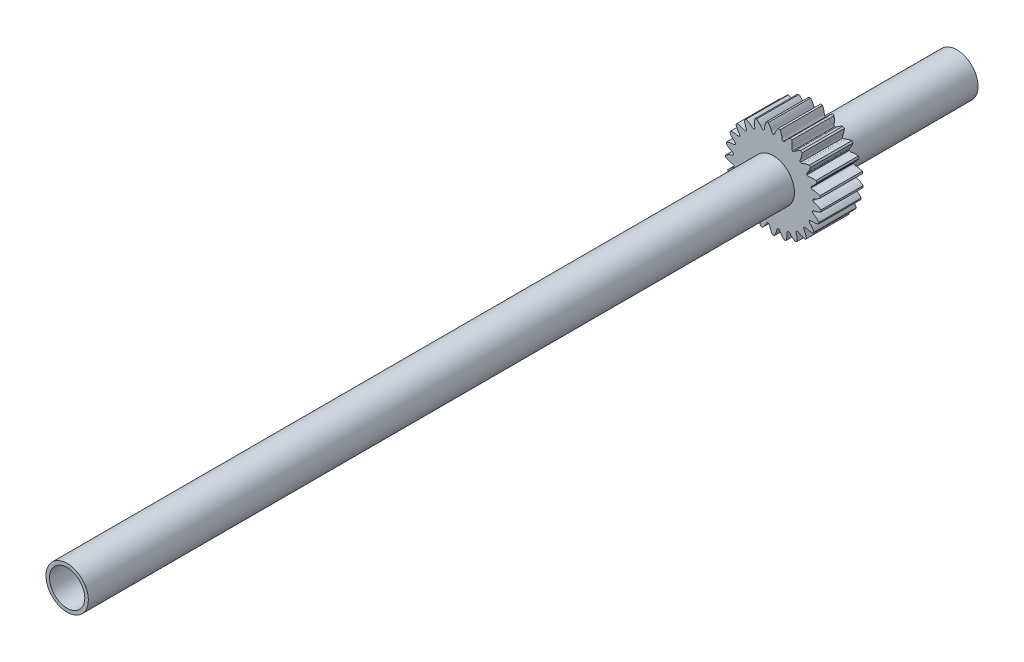
SolidWorks part; units mm, degrees
ref_plane "前视基准面" through (0, 0, 0) normal (0, 0, 1) x (1, 0, 0)
ref_plane "上视基准面" through (0, 0, 0) normal (0, 1, 0) x (1, 0, 0)
ref_plane "右视基准面" through (0, 0, 0) normal (1, 0, 0) x (0, 0, -1)
sketch "草图1" plane through (0, 0, 0) normal (0, 0, 1) x (1, 0, 0)
  circle A0 centre (0, 0) radius 33.75
extrude "凸台-拉伸1" add sketch "草图1" along normal blind 30
ref_axis "基准轴1" through (0, 0, 30) along (0, 0, -1)
sketch "草图2" plane through (0, 0, 0) normal (0, 0, 1) x (1, 0, 0)
  line L0 (0, 0) -> (0, 33.75) construction
  circle A0 centre (0, 0) radius 33.75 construction
  arc A1 (0.0063, 28.125) -> (-0.0063, 28.125) centre (0, 0) ccw
  arc A2 (9.0554, 38.365) -> (-9.0554, 38.365) centre (0, 0) ccw
  spline S0 degree 3 poles (0.0063, 28.125) (0.9043, 28.4223) (1.076, 29.1814) (1.3802, 29.9607) (1.4575, 30.1482) (1.5431, 30.3445) (1.6374, 30.5494) (1.7407, 30.7625) (1.8533, 30.9836) (1.9757, 31.2124) (2.1082, 31.4486) (2.2511, 31.6919) (2.4048, 31.9419) (2.5695, 32.1983) (2.7457, 32.4608) (2.9336, 32.729) (3.1335, 33.0025) (3.3457, 33.281) (3.5705, 33.564) (3.8081, 33.8513) (4.0588, 34.1423) (4.3228, 34.4367) (4.6004, 34.734) (4.8918, 35.0338) (5.1972, 35.3357) (5.5167, 35.6393) (5.8507, 35.944) (6.1991, 36.2495) (6.5623, 36.5552) (6.9404, 36.8607) (7.3334, 37.1656) (7.7415, 37.4693) (8.3121, 37.8764) (8.7539, 38.1718) (9.0554, 38.365) knots 0 0 0 0 0.152601 0.166415 0.181046 0.196494 0.21276 0.229843 0.247743 0.266461 0.285996 0.306348 0.327517 0.349503 0.372307 0.395928 0.420366 0.445621 0.471694 0.498584 0.526291 0.554815 0.584157 0.614315 0.645291 0.677085 0.709695 0.743123 0.777368 0.81243 0.84831 0.885006 0.92252 1 1 1 1
  spline S1 degree 3 poles (-0.0063, 28.125) (-0.9043, 28.4223) (-1.076, 29.1814) (-1.3802, 29.9607) (-1.4575, 30.1482) (-1.5431, 30.3445) (-1.6374, 30.5494) (-1.7407, 30.7625) (-1.8533, 30.9836) (-1.9757, 31.2124) (-2.1082, 31.4486) (-2.2511, 31.6919) (-2.4048, 31.9419) (-2.5695, 32.1983) (-2.7457, 32.4608) (-2.9336, 32.729) (-3.1335, 33.0025) (-3.3457, 33.281) (-3.5705, 33.564) (-3.8081, 33.8513) (-4.0588, 34.1423) (-4.3228, 34.4367) (-4.6004, 34.734) (-4.8918, 35.0338) (-5.1972, 35.3357) (-5.5167, 35.6393) (-5.8507, 35.944) (-6.1991, 36.2495) (-6.5623, 36.5552) (-6.9404, 36.8607) (-7.3334, 37.1656) (-7.7415, 37.4693) (-8.3121, 37.8764) (-8.7539, 38.1718) (-9.0554, 38.365) knots 0 0 0 0 0.152601 0.166415 0.181046 0.196494 0.21276 0.229843 0.247743 0.266461 0.285996 0.306348 0.327517 0.349503 0.372307 0.395928 0.420366 0.445621 0.471694 0.498584 0.526291 0.554815 0.584157 0.614315 0.645291 0.677085 0.709695 0.743123 0.777368 0.81243 0.84831 0.885006 0.92252 1 1 1 1
extrude "切除-拉伸1" cut sketch "草图2" along normal through all
pattern_circular "阵列(圆周)1" count 25 every 14.4 about axis through (0, 0, 30) along (0, 0, -1) of "切除-拉伸1"
sketch "草图3" plane through (0, 0, 0) normal (0, 0, 1) x (1, 0, 0)
  circle A0 centre (0, 0) radius 31.25 construction
  dimension "Dn" = 62.5
sketch "草图4" plane through (0, 0, 0) normal (0, 0, -1) x (-1, 0, 0)
  circle A0 centre (0, 0) radius 12.5
  dimension "D1" = 25
extrude "切除-拉伸2" cut sketch "草图4" against normal blind 30
sketch "草图5" plane through (0, 0, 30) normal (0, 0, 1) x (1, 0, 0)
  circle A0 centre (0, 0) radius 12.5
  circle A1 centre (0, 0) radius 15
  dimension "D1" = 25
  dimension "D2" = 30
extrude "凸台-拉伸2" add sketch "草图5" along normal blind 500 separate body
sketch "草图6" plane through (0, 0, 0) normal (0, 0, -1) x (-1, 0, 0)
  circle A0 centre (0, 0) radius 12.5
  circle A1 centre (0, 0) radius 15
  dimension "D1" = 30
  dimension "D2" = 25
extrude "凸台-拉伸3" add sketch "草图6" along normal blind 100 separate body
